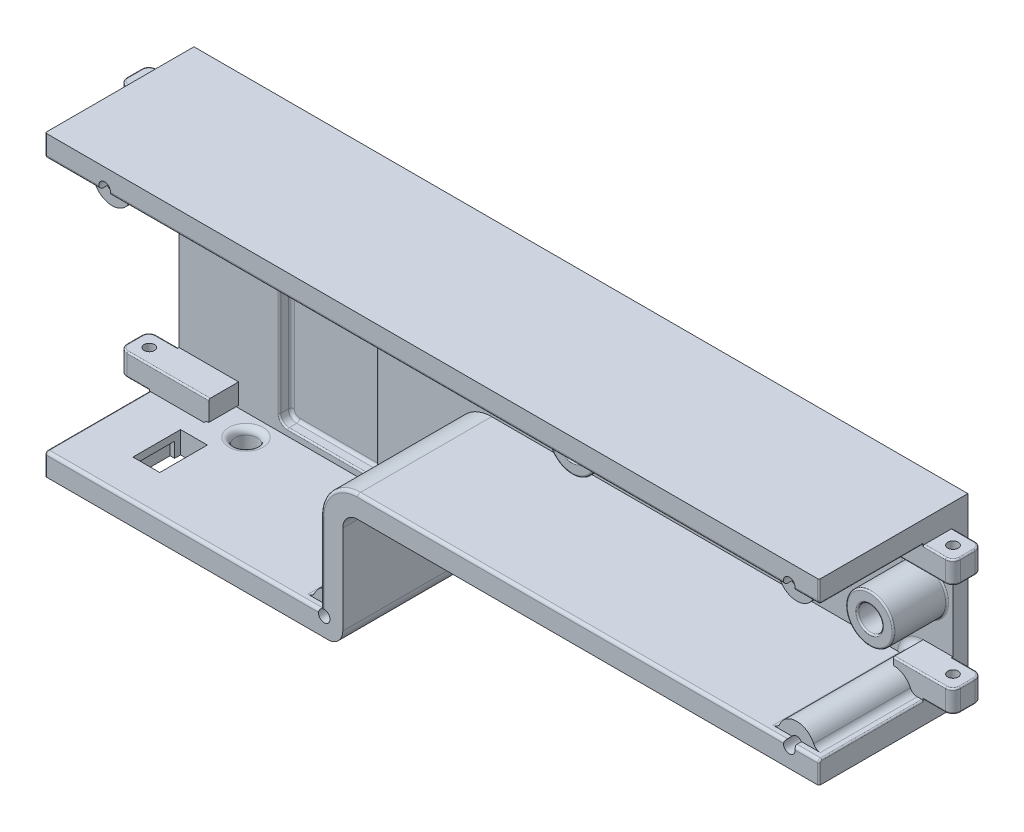
SolidWorks part; units mm, degrees
ref_plane "Front Plane" through (0, 0, 0) normal (0, 0, 1) x (1, 0, 0)
ref_plane "Top Plane" through (0, 0, 0) normal (0, 1, 0) x (1, 0, 0)
ref_plane "Right Plane" through (0, 0, 0) normal (1, 0, 0) x (0, 0, -1)
sketch "Sketch1" plane through (0, 0, 0) normal (0, 0, 1) x (1, 0, 0)
  line L0 (-50, 0) -> (0, 0) construction
  line L1 (-420, -70) -> (420, -70)
  line L2 (-420, -70) -> (-420, 70)
  line L3 (-420, 70) -> (420, 70)
  line L4 (420, -70) -> (420, 70)
  line L5 (-420, -70) -> (420, 70) construction
  line L6 (-420, 70) -> (420, -70) construction
  line L7 (0, 0) -> (50, 0) construction
  line L8 (250, 0) -> (350, 0) construction
  line L9 (333.7, -57.5) -> (333.7, 17.5)
  line L14 (334, -40) -> (350, 0) construction
  line L15 (334, 40) -> (334.4358, 38.9104) construction
  line L16 (336.5, 20.3) -> (363.5, 20.3)
  line L17 (366.3, -57.5) -> (366.3, 17.5)
  line L18 (336.5, -60.3) -> (363.5, -60.3)
  line L21 (365.5642, -38.9104) -> (366, -40) construction
  line L22 (365.5642, 38.9104) -> (366, 40) construction
  circle A0 centre (-350, 0) radius 4.15
  circle A1 centre (-250, 0) radius 4.15
  circle A2 centre (-150, 0) radius 4.15
  circle A3 centre (-50, 0) radius 4.15
  circle A4 centre (50, 0) radius 4.15
  circle A5 centre (150, 0) radius 4.15
  circle A6 centre (250, 0) radius 4.15
  circle A8 centre (350, 0) radius 4.15 [skipped]
  arc A13 (333.7, 17.5) -> (336.5, 20.3) centre (336.5, 17.5) cw
  arc A14 (363.5, 20.3) -> (366.3, 17.5) centre (363.5, 17.5) cw
  arc A15 (363.5, -60.3) -> (366.3, -57.5) centre (363.5, -57.5) ccw
  arc A16 (336.5, -60.3) -> (333.7, -57.5) centre (336.5, -57.5) cw
  point P0 (0, 0)
  dimension "D3" = 8.3
  dimension "D5" = 80
  dimension "D1" = 840
  dimension "D2" = 140
  dimension "D6" = 32
  dimension "D4" = 8
extrude "Boss-Extrude1" add sketch "Sketch1" along normal blind 5
sketch "Sketch2" plane through (0, 0, 5) normal (0, 0, 1) x (1, 0, 0)
  circle A0 centre (-350, 0) radius 8
  circle A1 centre (-350, 0) radius 4.15
extrude "Boss-Extrude3" add sketch "Sketch2" along normal blind 18
pattern_linear "LPattern1" count 7 spacing 100 along (1, 0, 0) of "Boss-Extrude3"
sketch "Sketch4" plane through (0, 0, 0) normal (0, 0, -1) x (-1, 0, 0)
  line L1 (-372.738, 24.1165) -> (-327.1271, 24.1165)
  line L2 (-372.738, 24.1165) -> (-372.738, -63.8212)
  line L3 (-372.738, -63.8212) -> (-327.1271, -63.8212)
  line L4 (-327.1271, 24.1165) -> (-327.1271, -63.8212)
extrude "Boss-Extrude4" add sketch "Sketch4" against normal blind 1
sketch "Sketch5" plane through (0, 70, 0) normal (0, 1, 0) x (1, 0, 0)
  line L4 (420, 0) -> (-420, 0)
  line L5 (-420, 0) -> (-420, -5)
  line L6 (-420, -5) -> (420, -5)
  line L7 (420, -5) -> (420, 0)
  line L8 (420, 0) -> (-420, 0)
  line L9 (-420, 0) -> (-420, -5)
  line L10 (-420, -5) -> (420, -5)
  line L11 (420, -5) -> (420, 0)
  dimension "D1" = 0
extrude "Cut-Extrude1" cut sketch "Sketch5" against normal blind 40
sketch "Sketch6" plane through (0, 0, 5) normal (0, 0, 1) x (1, 0, 0)
  line L0 (420, -70) -> (420, 30) construction
  line L1 (-420, -70) -> (300, -70)
  line L2 (-420, -70) -> (-420, -30)
  line L3 (-420, -30) -> (300, -30)
  line L4 (300, -70) -> (300, -30)
  dimension "D1" = 40
  dimension "D2" = 120
extrude "Cut-Extrude2" cut sketch "Sketch6" against normal through all
fillet "Fillet1" radius 5 4 edges at (300, -70, 2.5) (300, -30, 2.5) (-420, -30, 2.5) (-420, 30, 2.5)
fillet "Fillet2" radius 0.5 29 edges at (365.4799, -59.4799, 5) (350, -60.3, 5) (334.5201, -59.4799, 5) (333.7, -20, 5) (334.5201, 19.4799, 5) (350, 20.3, 5) (365.4799, 19.4799, 5) (-145.85, 0, 23) (-142, 0, 23) (-245.85, 0, 23) (-242, 0, 23) (366.3, -20, 5) (254.15, 0, 23) (258, 0, 23) (154.15, 0, 23) (158, 0, 23) (54.15, 0, 23) (58, 0, 23) (-45.85, 0, 23) (-42, 0, 23) (242, 0, 5) (142, 0, 5) (42, 0, 5) (-58, 0, 5) (-158, 0, 5) (-258, 0, 5) (-345.85, 0, 23) (-342, 0, 23) (-358, 0, 5)
fillet "Fillet3" radius 1 8 edges at (334.5201, 19.4799, 1) (333.7, -20, 1) (334.5201, -59.4799, 1) (350, -60.3, 1) (365.4799, -59.4799, 1) (366.3, -20, 1) (365.4799, 19.4799, 1) (350, 20.3, 1)
sketch "Sketch8" plane through (0, 0, 5) normal (0, 0, 1) x (1, 0, 0)
  line L0 (412.625, -62.625) -> (412.625, 22.625)
  line L1 (412.625, 22.625) -> (-412.625, 22.625)
  line L2 (-412.625, 22.625) -> (-412.625, -22.625)
  line L3 (-412.625, -22.625) -> (295, -22.625)
  line L4 (307.375, -35) -> (307.375, -62.625)
  line L5 (307.375, -62.625) -> (412.625, -62.625)
  line L6 (300, -35) -> (300, -65)
  line L7 (305, -70) -> (420, -70)
  line L8 (420, -70) -> (420, 30)
  line L9 (420, 30) -> (-415, 30)
  line L10 (-420, 25) -> (-420, -25)
  line L11 (-415, -30) -> (295, -30)
  line L12 (300, -35) -> (300, -65)
  line L13 (305, -70) -> (420, -70)
  line L14 (420, -70) -> (420, 30)
  line L15 (420, 30) -> (-415, 30)
  line L16 (-420, 25) -> (-420, -25)
  line L17 (-415, -30) -> (295, -30)
  arc A0 (-412.625, 22.625) -> (-412.625, 22.625) centre (-412.625, 22.625) ccw
  arc A1 (-412.625, -22.625) -> (-412.625, -22.625) centre (-412.625, -22.625) ccw
  arc A2 (307.375, -35) -> (295, -22.625) centre (295, -35) ccw
  arc A3 (307.375, -62.625) -> (307.375, -62.625) centre (307.375, -62.625) ccw
  arc A4 (300, -65) -> (305, -70) centre (305, -65) ccw
  arc A5 (-415, 30) -> (-420, 25) centre (-415, 25) ccw
  arc A6 (-420, -25) -> (-415, -30) centre (-415, -25) ccw
  arc A7 (300, -35) -> (295, -30) centre (295, -35) ccw
  arc A8 (300, -65) -> (305, -70) centre (305, -65) ccw
  arc A9 (-415, 30) -> (-420, 25) centre (-415, 25) ccw
  arc A10 (-420, -25) -> (-415, -30) centre (-415, -25) ccw
  arc A11 (300, -35) -> (295, -30) centre (295, -35) ccw
  dimension "D1" = 0
  dimension "D2" = 7.375
extrude "Boss-Extrude5" add sketch "Sketch8" along normal blind 45
ref_plane "Plane1" through (-140, 0, 0) normal (-1, 0, 0) x (0, 0, 1)
ref_plane "Plane2" through (140, 0, 0) normal (-1, 0, 0) x (0, 0, 1)
fillet "Fillet4" radius 1 3 edges at (307.375, -48.8125, 50) (303.7504, -26.2496, 50) (-58.8125, -22.625, 50)
sketch "Sketch10" plane through (0, 0, 50) normal (0, 0, 1) x (1, 0, 0)
  line L0 (412.625, -62.625) -> (412.625, 22.625) construction
  line L1 (412.625, 22.625) -> (420, 22.625)
  line L2 (412.625, 22.625) -> (412.625, -62.625)
  line L3 (412.625, -62.625) -> (420, -62.625)
  line L4 (420, 22.625) -> (420, -62.625)
  line L5 (412.625, -62.625) -> (412.625, 22.625) construction
  line L6 (420, -70) -> (420, 30) construction
extrude "Cut-Extrude3" cut sketch "Sketch10" against normal up to surface (45 mm away) up to face at (130.3304, -22.5267, 5)
fillet "Fillet5" radius 1 3 edges at (-412.625, -0.5, 50) (3.6875, 22.625, 50) (363.1875, -62.625, 50)
sketch "Sketch11" plane through (0, 0, 0) normal (0, 0, -1) x (-1, 0, 0)
  circle A0 centre (-250, 0) radius 4.15
  circle A1 centre (-150, 0) radius 4.15
  circle A2 centre (-50, 0) radius 4.15
  circle A3 centre (50, 0) radius 4.15
  circle A4 centre (150, 0) radius 4.15
  circle A5 centre (250, 0) radius 4.15
  circle A6 centre (350, 0) radius 4.15
  dimension "D1" = 7
extrude "Boss-Extrude6" add sketch "Sketch11" against normal blind 5
mirror "Mirror1" about plane through (420, -70, 5) normal (-1, 0, 0) of bodies 110
delete or keep bodies "Body-Delete/Keep 2" type delete bodies bodies 110
sketch "Sketch12" plane through (420, 0, 0) normal (-1, 0, 0) x (0, 0, 1)
  line L8 (50, 23.625) -> (50, 30)
  line L9 (50, 30) -> (0, 30)
  line L10 (0, 30) -> (0, -70)
  line L11 (0, -70) -> (50, -70)
  line L12 (50, -70) -> (50, -63.625)
  line L13 (49, -62.625) -> (5, -62.625)
  line L14 (5, -62.625) -> (5, 22.625)
  line L15 (5, 22.625) -> (49, 22.625)
  line L16 (50, 23.625) -> (50, 30)
  line L17 (50, 30) -> (0, 30)
  line L18 (0, 30) -> (0, -70)
  line L19 (0, -70) -> (50, -70)
  line L20 (50, -70) -> (50, -63.625)
  line L21 (49, -62.625) -> (5, -62.625)
  line L22 (5, -62.625) -> (5, 22.625)
  line L23 (5, 22.625) -> (49, 22.625)
  arc A2 (50, -63.625) -> (49, -62.625) centre (49, -63.625) ccw
  arc A3 (49, 22.625) -> (50, 23.625) centre (49, 23.625) ccw
  arc A4 (50, -63.625) -> (49, -62.625) centre (49, -63.625) ccw
  arc A5 (49, 22.625) -> (50, 23.625) centre (49, 23.625) ccw
  dimension "D1" = 0
extrude "Cut-Extrude4" cut sketch "Sketch12" against normal blind 20
sketch "Sketch13" plane through (0, -70, 0) normal (0, -1, 0) x (1, 0, 0)
  line L0 (535, 50) -> (440, 50) construction
  line L1 (455, 35) -> (467, 35)
  line L2 (455, 35) -> (455, 23)
  line L3 (455, 23) -> (467, 23)
  line L4 (467, 35) -> (467, 23)
  line L5 (440, 0) -> (440, 50) construction
  point P6 (455, 29)
  dimension "D1" = 12
  dimension "D2" = 12
  dimension "D3" = 15
  dimension "D4" = 15
extrude "Cut-Extrude5" cut sketch "Sketch13" against normal blind 5
sketch "Sketch14" plane through (0, -70, 0) normal (0, -1, 0) x (1, 0, 0)
  line L0 (467, 35) -> (455, 35) construction
  line L1 (456.5, 37) -> (465.5, 37)
  line L2 (456.5, 37) -> (456.5, 21)
  line L3 (456.5, 21) -> (465.5, 21)
  line L4 (465.5, 37) -> (465.5, 21)
  line L5 (455, 35) -> (455, 23) construction
  point P4 (461, 35)
  point P5 (455, 29)
  point P8 (461, 37)
  point P11 (456.5, 29)
  dimension "D1" = 9
  dimension "D2" = 16
extrude "Cut-Extrude6" cut sketch "Sketch14" against normal up to next
sketch "Sketch20" plane through (0, 0, 50) normal (0, 0, 1) x (1, 0, 0)
  line L0 (440, 30) -> (1255, 30) construction
  line L1 (1255, -30) -> (545, -30) construction
  line L2 (540, -35) -> (540, -65) construction
  line L3 (535, -70) -> (440, -70) construction
  line L5 (440, 23.625) -> (440, 30) construction
  line L12 (1255, 30) -> (440, 30)
  line L13 (440, 30) -> (440, 23.625)
  line L14 (440, 23.625) -> (1253.625, 23.625)
  line L15 (1253.625, 23.625) -> (1253.625, -23.625)
  line L16 (1253.625, -23.625) -> (545, -23.625)
  line L17 (533.625, -35) -> (533.625, -63.625)
  line L18 (533.625, -63.625) -> (440, -63.625)
  line L19 (440, -63.625) -> (440, -70)
  line L20 (440, -70) -> (535, -70)
  line L21 (540, -65) -> (540, -35)
  line L22 (545, -30) -> (1255, -30)
  line L23 (1260, -25) -> (1260, 25)
  line L35 (1260, -25) -> (1260, 25)
  circle A0 centre (790, 23.75) radius 1.95
  circle A1 centre (790, -23.75) radius 1.95
  circle A4 centre (460, 23.75) radius 1.95
  arc A5 (545, -23.625) -> (533.625, -35) centre (545, -35) ccw
  arc A6 (535, -70) -> (540, -65) centre (535, -65) ccw
  arc A7 (545, -30) -> (540, -35) centre (545, -35) ccw
  arc A8 (1255, -30) -> (1260, -25) centre (1255, -25) ccw
  arc A9 (1260, 25) -> (1255, 30) centre (1255, 25) ccw
  arc A11 (535, -70) -> (540, -65) centre (535, -65) ccw
  arc A12 (545, -30) -> (540, -35) centre (545, -35) ccw
  arc A13 (1255, -30) -> (1260, -25) centre (1255, -25) ccw
  arc A14 (1260, 25) -> (1255, 30) centre (1255, 25) ccw
  circle A15 centre (533.75, -63.75) radius 1.95
  circle A16 centre (690, 23.75) radius 1.95
  circle A17 centre (890, -23.75) radius 1.95
  circle A18 centre (990, 23.75) radius 1.95
  circle A19 centre (690, -23.75) radius 1.95
  circle A20 centre (890, 23.75) radius 1.95
  circle A21 centre (990, -23.75) radius 1.95
  circle A22 centre (1190, 23.75) radius 1.95
  circle A23 centre (1253.75, -23.75) radius 1.95
  point P13 (890, 0)
  point P28 (790, 0)
  point P44 (690, 0)
  point P46 (689.7552, 26.25)
  point P49 (990, 0)
  point P63 (1190, 0)
  dimension "D3" = 20
  dimension "D4" = 3.9
  dimension "D5" = 6.25
  dimension "D2" = 6.25
  dimension "D6" = 6.25
  dimension "D7" = 6.25
  dimension "D8" = 6.25
  dimension "D9" = 6.25
  dimension "D10" = 6.25
  dimension "D11" = 6.25
  dimension "D1" = 0
extrude "Cut-Extrude8" cut sketch "Sketch20" against normal blind 26 contours A4 | A15 | A16 | A19 | A20 | A17 | A18 | A21 | A22 | A23 | A1 | A0
ref_plane "Plane5" through (700, 0, 0) normal (-1, 0, 0) x (0, 0, 1)
ref_plane "Plane6" through (980, 0, 0) normal (-1, 0, 0) x (0, 0, 1)
ref_plane "Plane7" through (0, 0, 47.5) normal (0, 0, 1) x (1, 0, 0)
sketch "Sketch22" plane through (0, 0, 47.5) normal (0, 0, 1) x (1, 0, 0)
  circle A0 centre (460, 23.75) radius 1.95
  circle A1 centre (460, 23.75) radius 6.25
  circle A2 centre (690, 23.75) radius 1.95
  circle A3 centre (690, 23.75) radius 6.25
  circle A4 centre (790, 23.75) radius 1.95
  circle A5 centre (790, 23.75) radius 6.25
  circle A6 centre (890, 23.75) radius 1.95
  circle A7 centre (890, 23.75) radius 6.25
  circle A8 centre (990, 23.75) radius 1.95
  circle A9 centre (990, 23.75) radius 6.25
  circle A10 centre (1190, 23.75) radius 1.95
  circle A11 centre (1190, 23.75) radius 6.25
  circle A12 centre (1253.75, -23.75) radius 1.95
  circle A13 centre (1253.75, -23.75) radius 6.25
  circle A14 centre (990, -23.75) radius 1.95
  circle A16 centre (990, -23.75) radius 6.25
  circle A17 centre (890, -23.75) radius 1.95
  circle A18 centre (890, -23.75) radius 6.25
  circle A19 centre (790, -23.75) radius 1.95
  circle A20 centre (790, -23.75) radius 6.25
  circle A21 centre (690, -23.75) radius 1.95
  circle A22 centre (690, -23.75) radius 6.25
  circle A23 centre (533.75, -63.75) radius 1.95
  circle A24 centre (533.75, -63.75) radius 6.25
extrude "Boss-Extrude8" add sketch "Sketch22" against normal up to surface (42.5 mm away) up to face at (1198.5, 0, 5)
sketch "Sketch23" plane through (0, 0, 5) normal (0, 0, 1) x (1, 0, 0)
  line L1 (461.5928, 22.625) -> (458.4072, 22.625)
  line L2 (461.5928, 22.625) -> (458.4072, 22.625)
  line L3 (691.5928, 22.625) -> (688.4072, 22.625)
  line L4 (691.5928, 22.625) -> (688.4072, 22.625)
  line L5 (791.5928, 22.625) -> (788.4072, 22.625)
  line L6 (791.5928, 22.625) -> (788.4072, 22.625)
  line L7 (891.5928, 22.625) -> (888.4072, 22.625)
  line L8 (891.5928, 22.625) -> (888.4072, 22.625)
  line L9 (991.5928, 22.625) -> (988.4072, 22.625)
  line L10 (991.5928, 22.625) -> (988.4072, 22.625)
  line L11 (1191.5928, 22.625) -> (1188.4072, 22.625)
  line L12 (1191.5928, 22.625) -> (1188.4072, 22.625)
  line L13 (988.4072, -22.625) -> (991.5928, -22.625)
  line L14 (1252.1572, -22.625) -> (1252.625, -22.625)
  line L15 (1252.625, -22.625) -> (1252.625, -22.1572)
  line L16 (1252.1572, -22.625) -> (1252.625, -22.625)
  line L17 (1252.625, -22.625) -> (1252.625, -22.1572)
  line L18 (988.4072, -22.625) -> (991.5928, -22.625)
  line L19 (888.4072, -22.625) -> (891.5928, -22.625)
  line L20 (888.4072, -22.625) -> (891.5928, -22.625)
  line L21 (788.4072, -22.625) -> (791.5928, -22.625)
  line L22 (788.4072, -22.625) -> (791.5928, -22.625)
  line L23 (688.4072, -22.625) -> (691.5928, -22.625)
  line L24 (688.4072, -22.625) -> (691.5928, -22.625)
  line L26 (532.1572, -62.625) -> (532.625, -62.625)
  line L27 (532.625, -62.625) -> (532.625, -62.1572)
  line L28 (532.1572, -62.625) -> (532.625, -62.625)
  line L29 (532.625, -62.625) -> (532.625, -62.1572)
  arc A1 (458.4072, 22.625) -> (461.5928, 22.625) centre (460, 23.75) ccw
  arc A2 (458.4072, 22.625) -> (461.5928, 22.625) centre (460, 23.75) ccw
  arc A3 (688.4072, 22.625) -> (691.5928, 22.625) centre (690, 23.75) ccw
  arc A4 (688.4072, 22.625) -> (691.5928, 22.625) centre (690, 23.75) ccw
  arc A5 (788.4072, 22.625) -> (791.5928, 22.625) centre (790, 23.75) ccw
  arc A6 (788.4072, 22.625) -> (791.5928, 22.625) centre (790, 23.75) ccw
  arc A7 (888.4072, 22.625) -> (891.5928, 22.625) centre (890, 23.75) ccw
  arc A8 (888.4072, 22.625) -> (891.5928, 22.625) centre (890, 23.75) ccw
  arc A9 (988.4072, 22.625) -> (991.5928, 22.625) centre (990, 23.75) ccw
  arc A10 (988.4072, 22.625) -> (991.5928, 22.625) centre (990, 23.75) ccw
  arc A11 (1188.4072, 22.625) -> (1191.5928, 22.625) centre (1190, 23.75) ccw
  arc A12 (1188.4072, 22.625) -> (1191.5928, 22.625) centre (1190, 23.75) ccw
  arc A13 (1252.625, -22.1572) -> (1252.1572, -22.625) centre (1253.75, -23.75) ccw
  arc A14 (1252.625, -22.1572) -> (1252.1572, -22.625) centre (1253.75, -23.75) ccw
  arc A15 (991.5928, -22.625) -> (988.4072, -22.625) centre (990, -23.75) ccw
  arc A16 (991.5928, -22.625) -> (988.4072, -22.625) centre (990, -23.75) ccw
  arc A17 (891.5928, -22.625) -> (888.4072, -22.625) centre (890, -23.75) ccw
  arc A18 (891.5928, -22.625) -> (888.4072, -22.625) centre (890, -23.75) ccw
  arc A19 (791.5928, -22.625) -> (788.4072, -22.625) centre (790, -23.75) ccw
  arc A20 (791.5928, -22.625) -> (788.4072, -22.625) centre (790, -23.75) ccw
  arc A21 (691.5928, -22.625) -> (688.4072, -22.625) centre (690, -23.75) ccw
  arc A22 (691.5928, -22.625) -> (688.4072, -22.625) centre (690, -23.75) ccw
  arc A23 (532.625, -62.1572) -> (532.1572, -62.625) centre (533.75, -63.75) ccw
  arc A24 (532.625, -62.1572) -> (532.1572, -62.625) centre (533.75, -63.75) ccw
  dimension "D1" = 0
  dimension "D2" = 0
  dimension "D3" = 0
  dimension "D4" = 0
  dimension "D5" = 0
  dimension "D6" = 0
  dimension "D7" = 0
  dimension "D8" = 0
  dimension "D9" = 0
  dimension "D10" = 0
  dimension "D11" = 0
  dimension "D12" = 0
extrude "Boss-Extrude9" add sketch "Sketch23" along normal up to surface (19 mm away) up to face at (460, 24.1625, 24)
fillet "Fillet6" radius 2.5 36 edges at (1252.625, -17.6021, 26.25) (1247.6021, -22.625, 26.25) (1249.3306, -19.3306, 5) (996.1479, -22.625, 26.25) (990, -17.5, 5) (983.8521, -22.625, 26.25) (890, -17.5, 5) (883.8521, -22.625, 26.25) (896.1479, -22.625, 26.25) (796.1479, -22.625, 26.25) (783.8521, -22.625, 26.25) (790, -17.5, 5) (696.1479, -22.625, 26.25) (690, -17.5, 5) (683.8521, -22.625, 26.25) (532.625, -57.6021, 26.25) (529.3306, -59.3306, 5) (527.6021, -62.625, 26.25) (453.8521, 22.625, 26.25) (466.1479, 22.625, 26.25) (683.8521, 22.625, 26.25) (696.1479, 22.625, 26.25) (783.8521, 22.625, 26.25) (796.1479, 22.625, 26.25) (896.1479, 22.625, 26.25) (883.8521, 22.625, 26.25) (983.8521, 22.625, 26.25) (996.1479, 22.625, 26.25) (1196.1479, 22.625, 26.25) (1183.8521, 22.625, 26.25) (1190, 17.5, 5) (990, 17.5, 5) (890, 17.5, 5) (790, 17.5, 5) (690, 17.5, 5) (460, 17.5, 5)
ref_plane "Plane8" through (700, 0, 0) normal (-1, 0, 0) x (0, 0, 1)
sketch "Sketch24" plane through (700, 0, 0) normal (-1, 0, 0) x (0, 0, 1)
  line L1 (-38.0161, 54.9717) -> (86.0235, 54.9717)
  line L2 (-38.0161, 54.9717) -> (-38.0161, -88.7448)
  line L3 (-38.0161, -88.7448) -> (86.0235, -88.7448)
  line L4 (86.0235, 54.9717) -> (86.0235, -88.7448)
extrude "Cut-Extrude9" cut sketch "Sketch24" against normal through all
sketch "Sketch25" plane through (0, 0, 5) normal (0, 0, 1) x (1, 0, 0)
  line L0 (690, 15) -> (700, 15)
  line L1 (700, -22.625) -> (700, 22.625) construction
  line L2 (700, 15) -> (700, 22.625)
  line L3 (700, 22.625) -> (691.5928, 22.625)
  line L4 (690, 15) -> (690, 21.8)
  arc A0 (681.3226, 22.625) -> (698.6774, 22.625) centre (690, 23.75) ccw construction
  circle A1 centre (690, 23.75) radius 1.95 construction
  arc A2 (690, 21.8) -> (691.5928, 22.625) centre (690, 23.75) ccw
extrude "Boss-Extrude10" add sketch "Sketch25" along normal blind 10 contours A2 L3 L2 L0 L4
sketch "Sketch26" plane through (700, 0, 0) normal (1, 0, 0) x (0, 0, -1)
  line L0 (-47.5, 22.625) -> (-15, 22.625) construction
  line L1 (-15, 15) -> (-5.125, 15)
  line L2 (-15, 15) -> (-15, 22.5)
  line L3 (-15, 22.5) -> (-5.125, 22.5)
  line L4 (-5.125, 15) -> (-5.125, 22.5)
  line L5 (-5, -22.625) -> (-5, 15) construction
  dimension "D1" = 0.125
  dimension "D2" = 0.125
extrude "Boss-Extrude11" add sketch "Sketch26" along normal blind 10
fillet "Fillet7" radius 2.5 2 edges at (710, 18.75, 5.125) (710, 18.75, 15)
fillet "Fillet8" radius 0.5 10 edges at (698.75, 15, 15) (709.2678, 15, 14.2678) (703.75, 15, 5.125) (709.2678, 15, 5.8572) (703.75, 22.5, 5.125) (709.2678, 22.5, 5.8572) (703.75, 22.5, 15) (709.2678, 22.5, 14.2678) (710, 15, 10.0625) (710, 22.5, 10.0625)
sketch "Sketch27" plane through (0, 22.5, 0) normal (0, 1, 0) x (1, 0, 0)
  line L2 (710, -7.625) -> (710, -12.5) construction
  circle A0 centre (705, -10) radius 1.75
  dimension "D1" = 5
  dimension "D2" = 5
mirror "Mirror2" about plane through (0, 0, 0) normal (0, 1, 0) of "Fillet8", "Fillet7", "Boss-Extrude11", "Boss-Extrude10"
extrude "Cut-Extrude10" cut sketch "Sketch27" against normal mid plane 110
fillet "Fillet9" radius 0.5 6 edges at (700, 22.625, 32) (700, 22.9179, 49.7071) (700, -22.625, 32) (700, -22.9179, 49.7071) (700, 26.8125, 50) (700, -26.8125, 50)
sketch "Sketch28" plane through (0, -70, 0) normal (0, -1, 0) x (1, 0, 0)
  circle A0 centre (469.7441, 12.2499) radius 3.75
extrude "Cut-Extrude11" cut sketch "Sketch28" against normal up to next
fillet "Fillet10" radius 2 1 edges at (469.7441, -62.625, 15.9999)
sketch "Sketch29" plane through (0, 0, 5) normal (0, 0, 1) x (1, 0, 0)
  line L0 (460, 21.8) -> (460, 15)
  line L1 (460, 15) -> (440, 15)
  line L2 (440, -62.625) -> (440, 22.625) construction
  line L3 (440, 15) -> (440, 22.625)
  line L4 (440, 22.625) -> (458.4072, 22.625)
  arc A0 (458.4072, 22.625) -> (461.5928, 22.625) centre (460, 23.75) ccw construction
  circle A1 centre (460, 23.75) radius 1.95 construction
  arc A2 (458.4072, 22.625) -> (460, 21.8) centre (460, 23.75) ccw
  arc A3 (451.3226, 22.625) -> (468.6774, 22.625) centre (460, 23.75) ccw construction
extrude "Boss-Extrude12" add sketch "Sketch29" along normal blind 10
sketch "Sketch30" plane through (440, 0, 0) normal (-1, 0, 0) x (0, 0, 1)
  line L0 (15, 22.625) -> (47.5, 22.625) construction
  line L1 (15, 15) -> (5.125, 15)
  line L2 (15, 15) -> (15, 22.5)
  line L3 (15, 22.5) -> (5.125, 22.5)
  line L4 (5.125, 15) -> (5.125, 22.5)
  line L5 (5, -62.625) -> (5, 15) construction
  dimension "D1" = 0.125
  dimension "D2" = 0.125
extrude "Boss-Extrude13" add sketch "Sketch30" along normal blind 10
fillet "Fillet11" radius 2.5 2 edges at (430, 18.75, 5.125) (430, 18.75, 15)
fillet "Fillet12" radius 0.5 13 edges at (436.25, 22.5, 5.125) (430.7322, 22.5, 5.8572) (430, 22.5, 10.0625) (430.7322, 22.5, 14.2678) (436.25, 15, 5.125) (430.7322, 15, 5.8572) (430, 15, 10.0625) (430.7322, 15, 14.2678) (440, 22.625, 32) (440, 22.9179, 49.7071) (436.25, 22.5, 15) (446.25, 15, 15) (440, 26.8125, 50)
ref_plane "Plane10" through (0, -20, 0) normal (0, 1, 0) x (1, 0, 0)
mirror "Mirror3" about plane through (0, -20, 0) normal (0, 1, 0) of "Fillet12", "Fillet11", "Boss-Extrude13", "Boss-Extrude12"
sketch "Sketch31" plane through (0, 22.5, 0) normal (0, 1, 0) x (1, 0, 0)
  line L0 (440, -14.5) -> (440, -5.625) construction
  circle A0 centre (435, -10) radius 1.75
  dimension "D1" = 5
  dimension "D2" = 5
extrude "Cut-Extrude12" cut sketch "Sketch31" against normal through all
